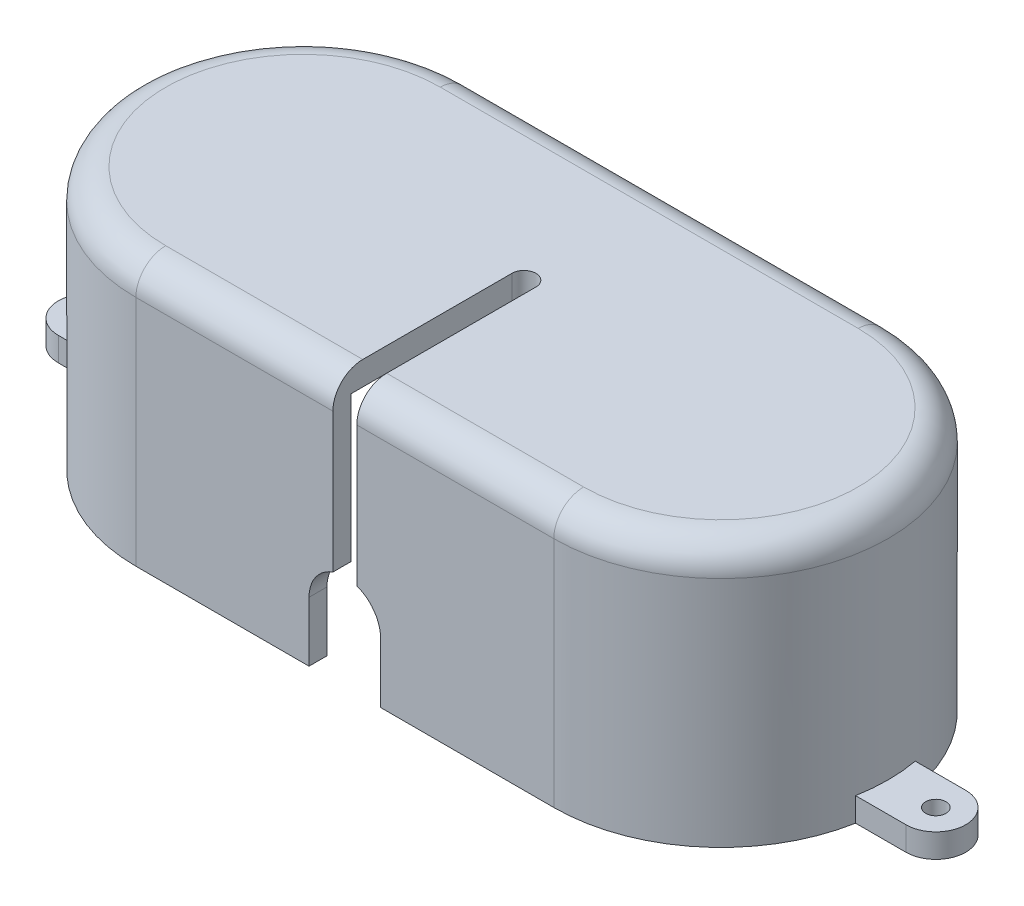
SolidWorks part; units mm, degrees
ref_plane "Front Plane" through (0, 0, 0) normal (0, 0, 1) x (1, 0, 0)
ref_plane "Top Plane" through (0, 0, 0) normal (0, 1, 0) x (1, 0, 0)
ref_plane "Right Plane" through (0, 0, 0) normal (1, 0, 0) x (0, 0, -1)
sketch "Sketch1" plane through (0, 0, 0) normal (0, 1, 0) x (1, 0, 0)
  line L0 (-35, 0) -> (35, 0) construction
  line L1 (-35, 25) -> (35, 25)
  line L2 (-35, -25) -> (35, -25)
  line L3 (-35, 28) -> (35, 28)
  line L4 (-35, -28) -> (35, -28)
  arc A0 (-35, 25) -> (-35, -25) centre (-35, 0) ccw
  arc A1 (35, -25) -> (35, 25) centre (35, 0) ccw
  arc A2 (35, -28) -> (35, 28) centre (35, 0) ccw
  arc A3 (-35, 28) -> (-35, -28) centre (-35, 0) ccw
  point P2 (0, 0)
  dimension "D3" = 25
  dimension "D1" = 3
  dimension "D2" = 70
extrude "Boss-Extrude1" add sketch "Sketch1" along normal blind 40
extrude "Boss-Extrude2" add sketch "Sketch1<2>" along normal blind 4 from surface contours A2 L3 A3 L4 starting at face at (0, 40, 0)
sketch "Sketch1<2>" plane through (0, 0, 0) normal (0, 1, 0) x (1, 0, 0) same geometry as "Sketch1"
sketch "Sketch3" plane through (0, 0, 0) normal (0, -1, 0) x (1, 0, 0)
  line L0 (-71, 5) -> (-62.55, 5)
  line L1 (-71, -5) -> (-62.55, -5)
  circle A0 centre (-71, 0) radius 1.7
  arc A1 (-71, 5) -> (-71, -5) centre (-71, 0) ccw
  arc A3 (-35, 28) -> (-35, -28) centre (-35, 0) ccw construction
  point P2 (0, 0)
  point P10 (-70.976, 1.3145)
  point P14 (0, 0)
  arc M4 (-35, 28) -> (-35, -28) centre (-35, 0) ccw
  dimension "D1" = 3.4
  dimension "D2" = 10
  dimension "D3" = 8
extrude "Boss-Extrude3" add sketch "Sketch3" against normal blind 4 contours L0 A1 L1 A0 M4 region at (-68.7721, 0, 0)
mirror "Mirror1" about plane through (0, 0, 0) normal (1, 0, 0) of "Boss-Extrude3"
sketch "Sketch4" plane through (0, 0, 25) normal (0, 0, -1) x (-1, 0, 0)
  line L0 (6, 10) -> (6, 0)
  line L1 (35, 0) -> (-35, 0) construction
  line L2 (-6, 10) -> (-6, 0)
  line L3 (6, 0) -> (-6, 0)
  arc A0 (6, 10) -> (-6, 10) centre (0, 10) ccw
  point P1 (0, 0)
  point P9 (0, 0)
  dimension "D1" = 12
  dimension "D2" = 10
extrude "Cut-Extrude1" cut sketch "Sketch4" against normal blind 4
sketch "Sketch5" plane through (0, 0, 28) normal (0, 0, 1) x (1, 0, 0)
  line L1 (-2, 0) -> (2, 0)
  line L2 (-2, 0) -> (-2, 44)
  line L3 (-2, 44) -> (2, 44)
  line L4 (2, 0) -> (2, 44)
  line L5 (-35, 0) -> (-6, 0) construction
  line L6 (35, 44) -> (-35, 44) construction
  point P11 (0, 0)
  dimension "D1" = 4
extrude "Cut-Extrude2" cut sketch "Sketch5" against normal blind 30 contours L4 L3 L2 L1
sketch "Sketch6" plane through (0, 44, 0) normal (0, 1, 0) x (1, 0, 0)
  line L0 (-2, 2) -> (2, 2) construction
  circle A0 centre (0, 2) radius 2
extrude "Cut-Extrude3" cut sketch "Sketch6" against normal through all contours A0
fillet "Fillet1" radius 5 4 edges at (18.5, 44, 28) (-63, 44, 0) (0, 44, -28) (63, 44, 0)
